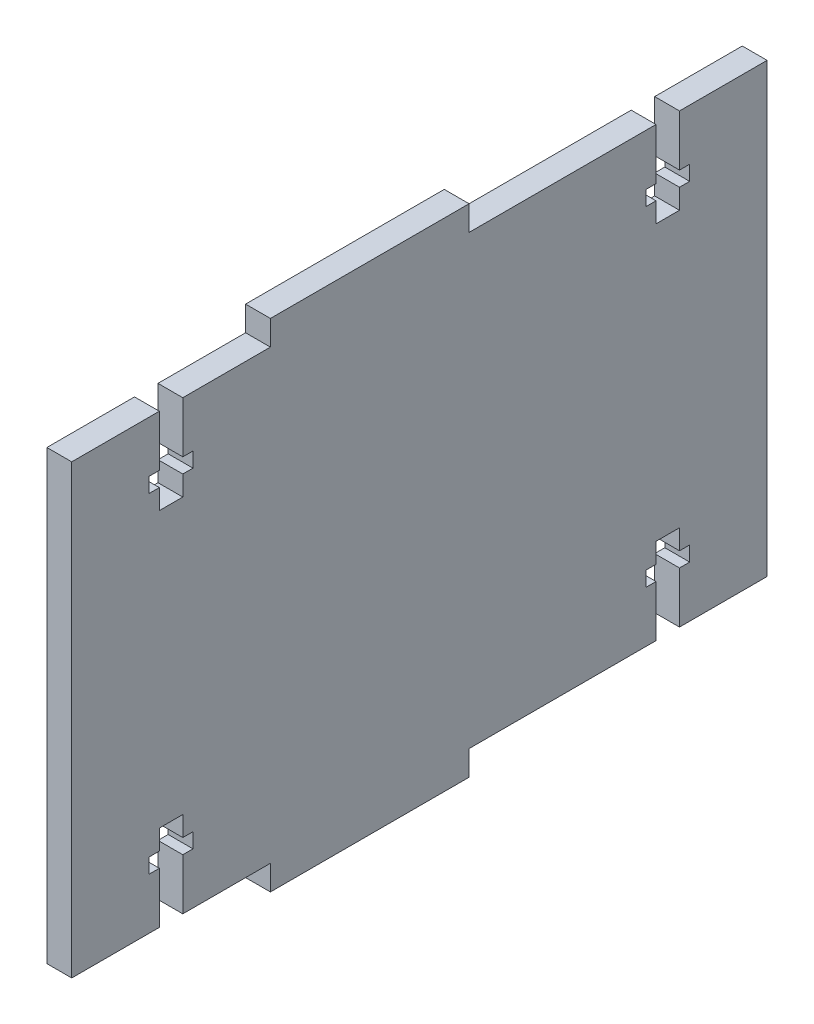
SolidWorks part; units mm, degrees
ref_plane "Front Plane" through (0, 0, 0) normal (0, 0, 1) x (1, 0, 0)
ref_plane "Top Plane" through (0, 0, 0) normal (0, 1, 0) x (1, 0, 0)
ref_plane "Right Plane" through (0, 0, 0) normal (1, 0, 0) x (0, 0, -1)
sketch "Sketch1" plane through (0, 0, 0) normal (1, 0, 0) x (0, 0, -1)
  line L1 (-44.45, -31.75) -> (44.45, -31.75)
  line L2 (-44.45, -31.75) -> (-44.45, 31.75)
  line L3 (-44.45, 31.75) -> (44.45, 31.75)
  line L4 (44.45, -31.75) -> (44.45, 31.75)
  line L5 (-44.45, -31.75) -> (44.45, 31.75) construction
  line L6 (-44.45, 31.75) -> (44.45, -31.75) construction
  point P0 (0, 0)
  dimension "D1" = 88.9
  dimension "D2" = 63.5
extrude "Boss-Extrude1" add sketch "Sketch1" along normal blind 3.175
sketch "Sketch2" plane through (3.175, 0, 0) normal (1, 0, 0) x (0, 0, -1)
  line L0 (-44.45, -31.75) -> (44.45, -31.75) construction
  line L1 (-44.45, -31.75) -> (44.45, -31.75) construction
  line L2 (-19.05, -31.75) -> (-19.05, -28.575) construction
  line L3 (-19.05, 31.75) -> (-19.05, 28.575) construction
  line L4 (44.45, -31.75) -> (6.35, -31.75)
  line L5 (-44.45, 0) -> (44.45, 0) construction
  line L6 (-44.45, 31.75) -> (-44.45, -31.75) construction
  line L7 (44.45, -31.75) -> (44.45, 31.75) construction
  line L8 (44.45, -31.75) -> (44.45, -28.575)
  line L9 (44.45, -28.575) -> (6.35, -28.575)
  line L10 (6.35, -31.75) -> (6.35, -28.575)
  line L11 (-19.05, 28.575) -> (-44.45, 28.575)
  line L12 (0, 31.75) -> (0, -31.75) construction
  line L13 (-19.05, 31.75) -> (-19.05, 28.575)
  line L14 (-19.05, 31.75) -> (-41.275, 31.75)
  line L15 (-44.45, 31.75) -> (-44.45, 28.575)
  line L16 (-44.45, 31.75) -> (-41.275, 31.75)
  line L17 (-44.45, -31.75) -> (-41.275, -31.75)
  line L18 (-44.45, -31.75) -> (-44.45, -28.575)
  line L19 (6.35, 31.75) -> (6.35, 28.575)
  line L20 (44.45, 28.575) -> (6.35, 28.575)
  line L21 (44.45, 31.75) -> (-44.45, 31.75) construction
  line L22 (44.45, 31.75) -> (44.45, 28.575)
  line L23 (44.45, 31.75) -> (6.35, 31.75)
  line L31 (-19.05, -31.75) -> (-41.275, -31.75)
  line L32 (-19.05, -31.75) -> (-19.05, -28.575)
  line L33 (-19.05, -28.575) -> (-44.45, -28.575)
  point P6 (0, -31.75)
  dimension "D1" = 3.175
  dimension "D2" = 19.05
  dimension "D3" = 25.4
extrude "Cut-Extrude1" cut sketch "Sketch2" against normal through all
sketch "Sketch3" plane through (3.175, 0, 0) normal (1, 0, 0) x (0, 0, -1)
  line L0 (-30.25, -17.575) -> (-30.25, -20.125)
  line L1 (-30.25, -17.575) -> (-33.25, -17.575)
  line L2 (-30.25, -28.575) -> (-33.25, -28.575)
  line L3 (-33.25, -17.575) -> (-33.25, -20.125)
  line L4 (-30.25, -17.575) -> (-33.25, -28.575) construction
  line L5 (-30.25, -28.575) -> (-33.25, -17.575) construction
  line L6 (-33.25, -22.025) -> (-33.25, -28.575)
  line L7 (-34.55, -22.025) -> (-34.55, -20.125)
  line L8 (-34.55, -22.025) -> (-33.25, -22.025)
  line L9 (-28.95, -22.025) -> (-28.95, -20.125)
  line L10 (-34.55, -20.125) -> (-33.25, -20.125)
  line L11 (-34.55, -22.025) -> (-28.95, -20.125) construction
  line L12 (-28.95, -22.025) -> (-34.55, -20.125) construction
  line L13 (-30.25, -22.025) -> (-30.25, -28.575)
  line L14 (-33.25, -20.125) -> (-33.25, -22.025) construction
  line L15 (-30.25, -17.575) -> (-30.25, -22.025) construction
  line L16 (-30.25, -22.025) -> (-28.95, -22.025)
  line L17 (-30.25, -20.125) -> (-28.95, -20.125)
  line L18 (-33.25, -20.125) -> (-30.25, -20.125) construction
  line L19 (-30.25, -22.025) -> (-33.25, -22.025) construction
  line L20 (-19.05, -28.575) -> (-44.45, -28.575) construction
  line L21 (33.25, -17.575) -> (33.25, -20.125)
  line L22 (33.25, -17.575) -> (30.25, -17.575)
  line L23 (33.25, -28.575) -> (30.25, -28.575)
  line L24 (30.25, -17.575) -> (30.25, -20.125)
  line L25 (33.25, -17.575) -> (30.25, -28.575) construction
  line L26 (33.25, -28.575) -> (30.25, -17.575) construction
  line L27 (30.25, -22.025) -> (30.25, -28.575)
  line L28 (28.95, -22.025) -> (28.95, -20.125)
  line L29 (28.95, -22.025) -> (30.25, -22.025)
  line L30 (34.55, -22.025) -> (34.55, -20.125)
  line L31 (28.95, -20.125) -> (30.25, -20.125)
  line L32 (28.95, -22.025) -> (34.55, -20.125) construction
  line L33 (34.55, -22.025) -> (28.95, -20.125) construction
  line L34 (33.25, -22.025) -> (33.25, -28.575)
  line L35 (30.25, -20.125) -> (30.25, -22.025) construction
  line L36 (33.25, -17.575) -> (33.25, -22.025) construction
  line L37 (33.25, -22.025) -> (34.55, -22.025)
  line L38 (33.25, -20.125) -> (34.55, -20.125)
  line L39 (30.25, -20.125) -> (33.25, -20.125) construction
  line L40 (33.25, -22.025) -> (30.25, -22.025) construction
  line L41 (44.45, -28.575) -> (6.35, -28.575) construction
  line L42 (44.45, -28.575) -> (44.45, 28.575) construction
  line L43 (-44.45, 0) -> (44.45, 0) construction
  line L44 (-44.45, 28.575) -> (-44.45, -28.575) construction
  line L45 (33.25, 22.025) -> (30.25, 22.025) construction
  line L46 (30.25, 20.125) -> (33.25, 20.125) construction
  line L47 (33.25, 17.575) -> (33.25, 22.025) construction
  line L48 (30.25, 20.125) -> (30.25, 22.025) construction
  line L49 (34.55, 22.025) -> (28.95, 20.125) construction
  line L50 (28.95, 22.025) -> (34.55, 20.125) construction
  line L51 (33.25, 28.575) -> (30.25, 17.575) construction
  line L52 (33.25, 17.575) -> (30.25, 28.575) construction
  line L53 (33.25, 20.125) -> (34.55, 20.125)
  line L54 (33.25, 22.025) -> (34.55, 22.025)
  line L55 (33.25, 22.025) -> (33.25, 28.575)
  line L56 (28.95, 20.125) -> (30.25, 20.125)
  line L57 (34.55, 22.025) -> (34.55, 20.125)
  line L58 (28.95, 22.025) -> (30.25, 22.025)
  line L59 (28.95, 22.025) -> (28.95, 20.125)
  line L60 (30.25, 22.025) -> (30.25, 28.575)
  line L61 (30.25, 17.575) -> (30.25, 20.125)
  line L62 (33.25, 28.575) -> (30.25, 28.575)
  line L63 (33.25, 17.575) -> (30.25, 17.575)
  line L64 (33.25, 17.575) -> (33.25, 20.125)
  line L65 (-30.25, 22.025) -> (-33.25, 22.025) construction
  line L66 (-33.25, 20.125) -> (-30.25, 20.125) construction
  line L67 (-30.25, 17.575) -> (-30.25, 22.025) construction
  line L68 (-33.25, 20.125) -> (-33.25, 22.025) construction
  line L69 (-28.95, 22.025) -> (-34.55, 20.125) construction
  line L70 (-34.55, 22.025) -> (-28.95, 20.125) construction
  line L71 (-30.25, 28.575) -> (-33.25, 17.575) construction
  line L72 (-30.25, 17.575) -> (-33.25, 28.575) construction
  line L73 (-30.25, 20.125) -> (-28.95, 20.125)
  line L74 (-30.25, 22.025) -> (-28.95, 22.025)
  line L75 (-30.25, 22.025) -> (-30.25, 28.575)
  line L76 (-34.55, 20.125) -> (-33.25, 20.125)
  line L77 (-28.95, 22.025) -> (-28.95, 20.125)
  line L78 (-34.55, 22.025) -> (-33.25, 22.025)
  line L79 (-34.55, 22.025) -> (-34.55, 20.125)
  line L80 (-33.25, 22.025) -> (-33.25, 28.575)
  line L81 (-33.25, 17.575) -> (-33.25, 20.125)
  line L82 (-30.25, 28.575) -> (-33.25, 28.575)
  line L83 (-30.25, 17.575) -> (-33.25, 17.575)
  line L84 (-30.25, 17.575) -> (-30.25, 20.125)
  point P0 (-31.75, -28.575)
  point P5 (-31.75, -21.075)
  point P17 (31.75, -28.575)
  point P22 (31.75, -21.075)
  point P52 (31.75, 21.075)
  point P53 (31.75, 28.575)
  point P66 (-31.75, 21.075)
  point P67 (-31.75, 28.575)
  dimension "D1" = 3
  dimension "D2" = 11
  dimension "D3" = 5.6
  dimension "D4" = 1.9
  dimension "D5" = 3.5
  dimension "D6" = 3
  dimension "D7" = 11
  dimension "D8" = 5.6
  dimension "D9" = 1.9
  dimension "D10" = 3.5
  dimension "D11" = 12.7
extrude "Cut-Extrude2" cut sketch "Sketch3" against normal through all
